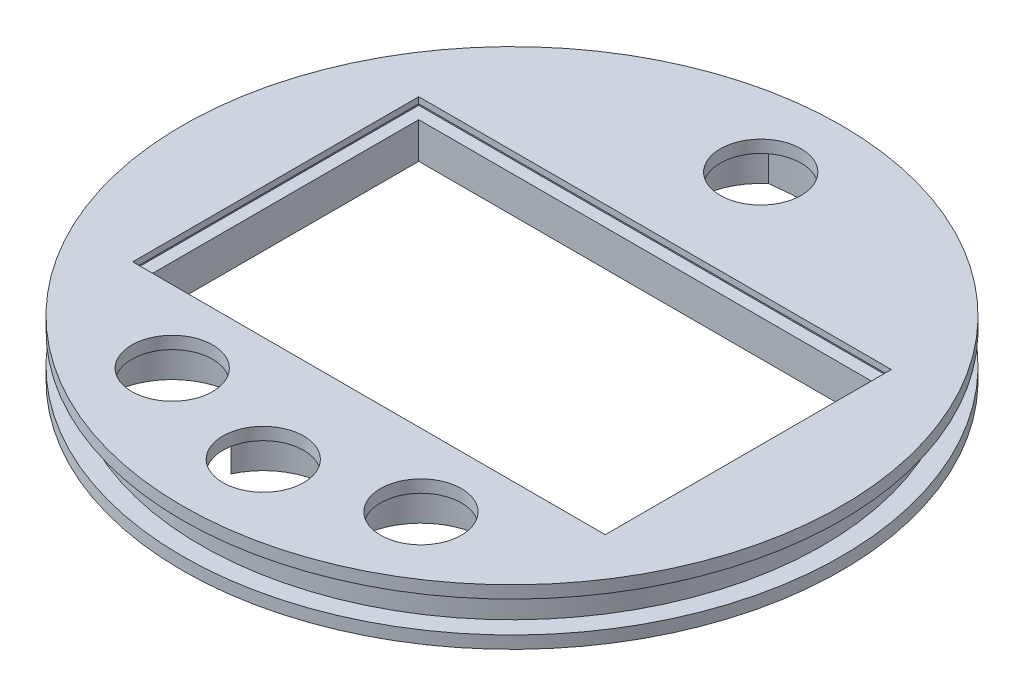
SolidWorks part; units mm, degrees
ref_plane "Front Plane" through (0, 0, 0) normal (0, 0, 1) x (1, 0, 0)
ref_plane "Top Plane" through (0, 0, 0) normal (0, 1, 0) x (1, 0, 0)
ref_plane "Right Plane" through (0, 0, 0) normal (1, 0, 0) x (0, 0, -1)
sketch "Sketch1" plane through (0, 0, 0) normal (0, 1, 0) x (1, 0, 0)
  line L0 (-20, -34.641) -> (0, 0)
  line L1 (0, 0) -> (20, -34.641)
  line L3 (-38, -23) -> (38, -23)
  line L4 (-38, -23) -> (-38, 23)
  line L5 (-38, 23) -> (38, 23)
  line L6 (38, -23) -> (38, 23)
  line L7 (-38, -23) -> (38, 23) construction
  line L8 (-38, 23) -> (38, -23) construction
  circle A0 centre (0, 0) radius 50
  circle A1 centre (0, 40) radius 6.5
  circle A2 centre (0, -40) radius 6.5
  circle A3 centre (20, -34.641) radius 6.5
  circle A4 centre (-20, -34.641) radius 6.5
  circle A5 centre (0, 0) radius 40 construction
  circle A6 centre (0, -40) radius 8 construction
  circle A7 centre (-20, -34.641) radius 8 construction
  dimension "D2" = 13
  dimension "D3" = 80
  dimension "D4" = 100
  dimension "D5" = 16
  dimension "D1" = 60
  dimension "D6" = 46
  dimension "D7" = 76
extrude "Boss-Extrude1" add sketch "Sketch1" along normal mid plane 2 contours A0 A4 A3 A2 A1 region at (-48.5858, 0, 0)
sketch "Sketch2" plane through (0, -1, 0) normal (0, -1, 0) x (1, 0, 0)
  circle A0 centre (0, 0) radius 50 construction
  circle A1 centre (0, 0) radius 50
  circle A2 centre (0, 0) radius 48.5
  circle A4 centre (0, -40) radius 6.5 construction
  point P0 (0, -46.5)
  point P4 (0, -46.5)
  point P5 (0, 0)
  point P6 (0, -48.5)
  dimension "D1" = 2
extrude "Boss-Extrude2" add sketch "Sketch2" along normal blind 7
sketch "Sketch3" plane through (0, 1, 0) normal (0, 1, 0) x (1, 0, 0)
  circle A0 centre (0, 0) radius 50 construction
  circle A1 centre (0, 0) radius 50
  circle A2 centre (0, 0) radius 53
  dimension "D1" = 3
extrude "Boss-Extrude3" add sketch "Sketch3" against normal blind 2
extrude "Boss-Extrude4" add sketch "Sketch3<2>" along normal blind 2 from surface starting at face at (0, -8, -50)
sketch "Sketch3<2>" plane through (0, 1, 0) normal (0, 1, 0) x (1, 0, 0) same geometry as "Sketch3"
sketch "Sketch5" plane through (0, -1, 0) normal (0, -1, 0) x (1, 0, 0)
  line L0 (-38, 23) -> (38, 23) construction
  line L1 (-38, 23) -> (-38, -23) construction
  line L2 (-38, -23) -> (38, -23) construction
  line L3 (38, 23) -> (38, -23) construction
  line L4 (-38, 23) -> (38, 23)
  line L5 (-38, 23) -> (-38, -23)
  line L6 (-38, -23) -> (38, -23)
  line L7 (38, 23) -> (38, -23)
  arc A0 (29.8765, 38.2053) -> (9.5465, 35.628) centre (20, 34.641) cw
  circle A1 centre (0, 0) radius 48.5
  circle A2 centre (0, 0) radius 48.5 construction
  arc A3 (9.5465, 35.628) -> (-9.5465, 35.628) centre (0, 40) cw
  arc A4 (-9.5465, 35.628) -> (-29.8765, 38.2053) centre (-20, 34.641) cw
  circle A5 centre (20, 34.641) radius 6.5 construction
  arc A6 (-6.7712, -48.025) -> (6.7712, -48.025) centre (0, -40) cw
  arc A7 (29.8765, 38.2053) -> (6.7712, -48.025) centre (0, 0) cw
  arc A8 (-29.8765, 38.2053) -> (-6.7712, -48.025) centre (0, 0) ccw
  point P17 (6.5, -48.025)
  point P25 (0, 0)
  point P26 (-9.5465, -47.5512)
  dimension "D2" = 4
  dimension "D1" = 0
extrude "Boss-Extrude5" add sketch "Sketch5" along normal through all
sketch "Sketch4" plane through (0, 0, 0) normal (0, 1, 0) x (1, 0, 0)
  line L1 (-40, -25) -> (40, -25)
  line L2 (-40, -25) -> (-40, 25)
  line L3 (-40, 25) -> (40, 25)
  line L4 (40, -25) -> (40, 25)
  line L5 (-40, -25) -> (40, 25) construction
  line L6 (-40, 25) -> (40, -25) construction
  point P0 (0, 0)
  dimension "D1" = 50
  dimension "D2" = 80
extrude "Cut-Extrude1" cut sketch "Sketch4" against normal blind 2.2
